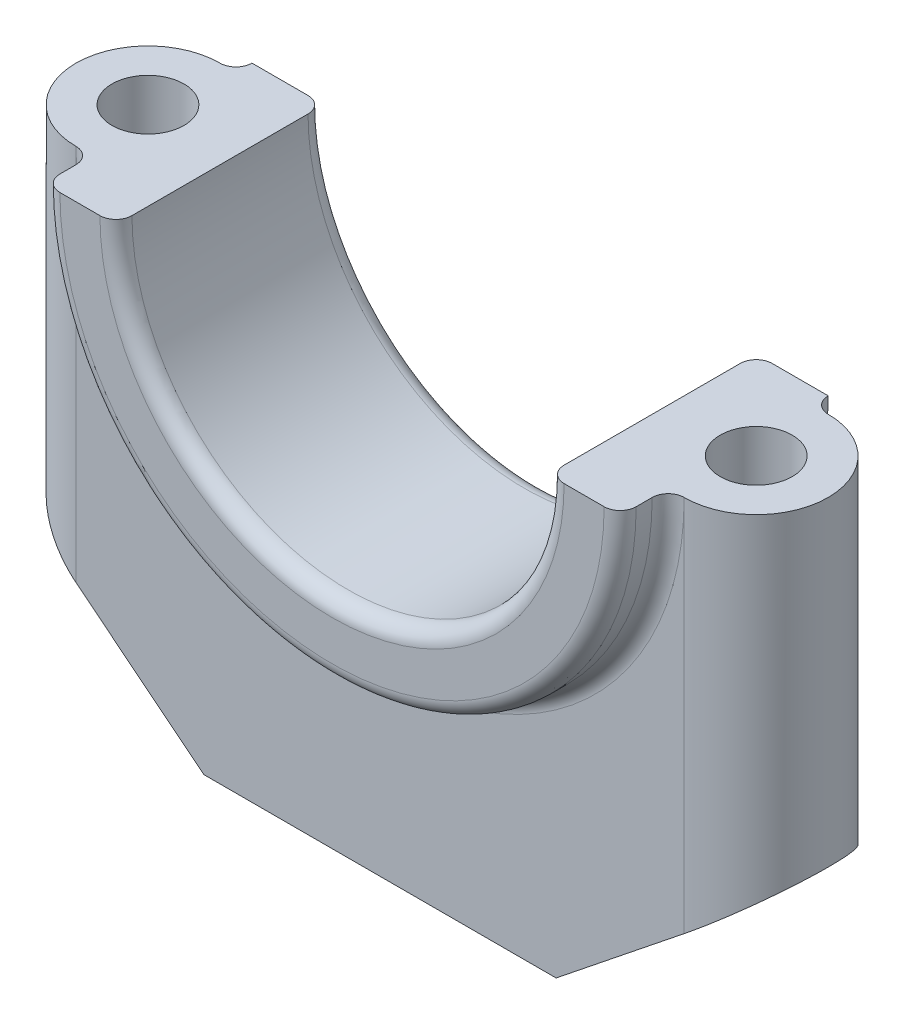
SolidWorks part; units mm, degrees
ref_plane "Front Plane" through (0, 0, 0) normal (0, 0, 1) x (1, 0, 0)
ref_plane "Top Plane" through (0, 0, 0) normal (0, 1, 0) x (1, 0, 0)
ref_plane "Right Plane" through (0, 0, 0) normal (1, 0, 0) x (0, 0, -1)
sketch "Sketch1" plane through (0, 0, 0) normal (0, 0, 1) x (1, 0, 0)
  line L0 (0, 0) -> (-11166.8033, 0) construction
  line L1 (0, 0) -> (0, 11166.8033) construction
  line L2 (-36, 0) -> (36, 0)
  line L3 (-36, 0) -> (-47, 0)
  line L4 (-47, 0) -> (-47, -40)
  line L5 (-47, -40) -> (-22, -60)
  line L6 (-22, -60) -> (22, -60)
  line L7 (47, -40) -> (22, -60)
  line L8 (47, 0) -> (47, -40)
  line L9 (36, 0) -> (47, 0)
  arc A0 (-27, 0) -> (27, 0) centre (0, 0) ccw
  arc A1 (-36, 0) -> (36, 0) centre (0, 0) ccw
  point P15 (0, -60)
  dimension "D1" = 54
  dimension "D2" = 72
  dimension "D3" = 47
  dimension "D4" = 20
  dimension "D5" = 25
  dimension "D6" = 60
extrude "Boss-Extrude1" add sketch "Sketch1" along normal blind 15 and the other way blind 11 contours L2 A1 A0 region at (-31.5, -0.805, 0)
extrude "Boss-Extrude2" add sketch "Sketch1<3>" along normal mid plane 18 contours A1 L3 L4 L5 L6 L7 L8 L9 region at (0, -37.1152, 0)
sketch "Sketch1<3>" plane through (0, 0, 0) normal (0, 0, 1) x (1, 0, 0) same geometry as "Sketch1"
fillet "Fillet1" 2 edges at (47, -20, -9) (47, -20, 9) type full round first side face at (0, -29.5, -9) second side face at (0, -29.5, 9) middle face at (47, -20, 0)
fillet "Fillet2" 2 edges at (-47, -20, 9) (-47, -20, -9) type full round first side face at (-2.25, -30.4, 9) second side face at (-2.25, -30.4, -9) middle face at (-47, -20, 0)
sketch "Sketch2" plane through (0, 0, 0) normal (0, 1, 0) x (1, 0, 0)
  line L0 (0, 0) -> (0, 50000) construction
  circle A0 centre (38, 0) radius 4.5
  arc A1 (38, -9) -> (38, 9) centre (38, 0) ccw construction
  circle A2 centre (-38, 0) radius 4.5
  dimension "D1" = 9
extrude "Cut-Extrude1" cut sketch "Sketch2" against normal blind 88
fillet "Fillet3" radius 2 3 edges at (0, -36, 15) (0, -36, -9) (0, -36, 9)
fillet "Fillet4" radius 2 2 edges at (0, -27, 15) (0, -27, -11)
